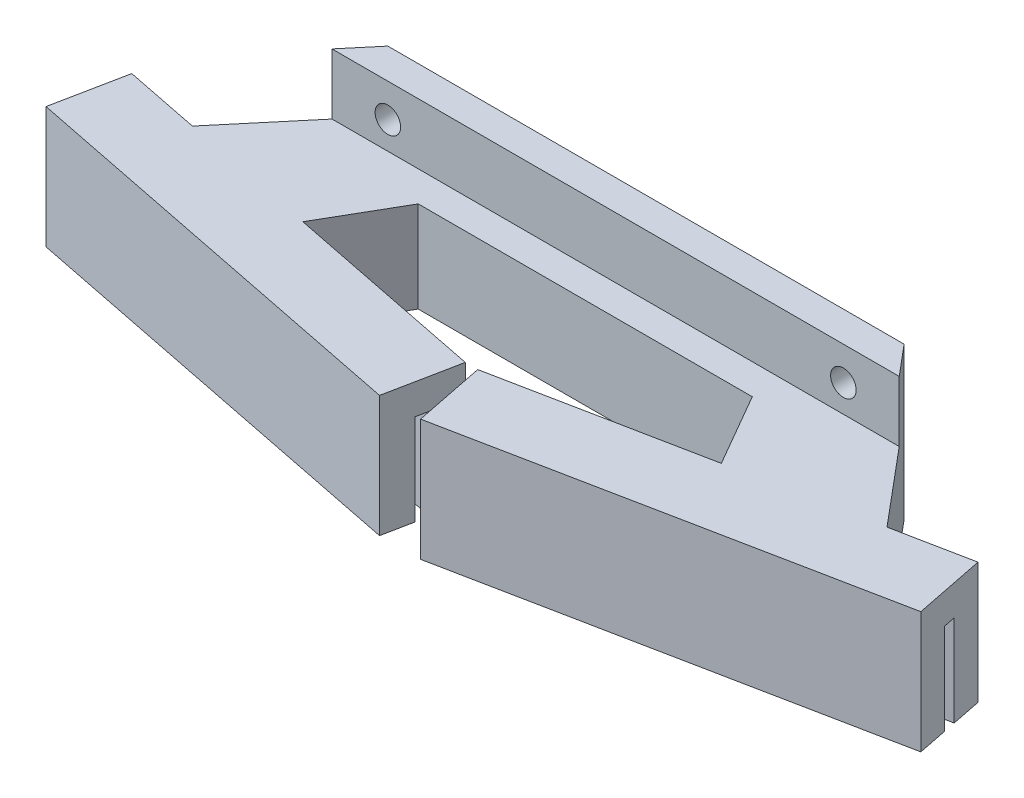
SolidWorks part; units mm, degrees
material "ABS"
ref_plane "Front Plane" through (0, 0, 0) normal (0, 0, 1) x (1, 0, 0)
ref_plane "Top Plane" through (0, 0, 0) normal (0, 1, 0) x (1, 0, 0)
ref_plane "Right Plane" through (0, 0, 0) normal (1, 0, 0) x (0, 0, -1)
ref_axis "X" through (-88.99, 0, 0) along (1, 0, 0)
ref_axis "Y" through (0, 55, 0) along (0, -1, 0)
ref_axis "Z" through (0, 0, -88.99) along (0, 0, 1)
sketch "Sketch1" plane through (0, 0, 0) normal (0, 1, 0) x (1, 0, 0)
  line L0 (27.1702, -94.8196) -> (27.5625, -96.7807) construction
  line L1 (27.1702, -94.8196) -> (27.5625, -96.7807)
  line L2 (22.7661, -96.7807) -> (23.1583, -94.8196) construction
  line L3 (-45.8746, -83.0526) -> (22.7661, -96.7807) construction
  line L4 (22.7661, -96.7807) -> (23.1583, -94.8196)
  line L5 (27.5625, -96.7807) -> (96.2031, -83.0526) construction
  line L6 (23.1583, -94.8196) -> (-45.4823, -81.0914)
  line L7 (-45.4823, -81.0914) -> (-45.8746, -83.0526)
  line L8 (-45.8746, -83.0526) -> (22.7661, -96.7807)
  line L9 (27.1702, -94.8196) -> (95.8109, -81.0914)
  line L10 (95.8109, -81.0914) -> (96.2031, -83.0526)
  line L11 (96.2031, -83.0526) -> (27.5625, -96.7807)
  dimension "D3" = 2
  dimension "D4" = 2
  dimension "D7" = 70
  dimension "D8" = 70
extrude "Boss-Extrude1" add sketch "Sketch1" along normal blind 5
sketch "Sketch2" plane through (0, 5, 0) normal (0, 1, 0) x (1, 0, 0)
  line L0 (0, 0) -> (0, 33.2136) construction
  line L1 (22.9622, -95.8001) -> (-45.6785, -82.072) construction
  line L2 (22.7661, -96.7807) -> (23.1583, -94.8196) construction
  line L3 (-45.4823, -81.0914) -> (-45.8746, -83.0526) construction
  line L4 (-45.4823, -81.0914) -> (-44.5018, -76.1885)
  line L5 (-44.5018, -76.1885) -> (24.1389, -89.9167)
  line L6 (24.1389, -89.9167) -> (23.1583, -94.8196)
  line L7 (23.1583, -94.8196) -> (-45.4823, -81.0914) construction
  line L8 (23.1583, -94.8196) -> (-45.4823, -81.0914)
  line L9 (21.7855, -101.6836) -> (22.7661, -96.7807)
  line L10 (-46.8552, -87.9555) -> (21.7855, -101.6836)
  line L11 (-45.8746, -83.0526) -> (-46.8552, -87.9555)
  line L12 (22.7661, -96.7807) -> (-45.8746, -83.0526)
  line L21 (27.1702, -94.8196) -> (26.1896, -89.9167)
  line L22 (26.1896, -89.9167) -> (94.8303, -76.1885)
  line L23 (94.8303, -76.1885) -> (95.8109, -81.0914)
  line L24 (96.2031, -83.0526) -> (95.8109, -81.0914) construction
  line L25 (95.8109, -81.0914) -> (27.1702, -94.8196) construction
  line L26 (95.8109, -81.0914) -> (27.1702, -94.8196)
  line L27 (27.3663, -95.8001) -> (96.007, -82.072) construction
  line L28 (27.1702, -94.8196) -> (27.5625, -96.7807) construction
  line L29 (97.1837, -87.9555) -> (96.2031, -83.0526)
  line L30 (28.543, -101.6836) -> (97.1837, -87.9555)
  line L31 (27.5625, -96.7807) -> (28.543, -101.6836)
  line L32 (96.2031, -83.0526) -> (27.5625, -96.7807)
  dimension "D1" = 5
  dimension "D2" = 5
extrude "Boss-Extrude2" add sketch "Sketch2" against normal blind 20
ref_plane "Plane1" through (0, -10, 0) normal (0, 1, 0) x (1, 0, 0)
sketch "Sketch3" plane through (0, -10, 0) normal (0, 1, 0) x (1, 0, 0)
  line L0 (25.1643, -107.258) -> (25.1643, -89.9167) construction
  line L1 (-17.3357, -61.1885) -> (67.6643, -61.1885)
  line L3 (-2.3357, -71.1885) -> (52.6643, -71.1885)
  line L5 (24.1389, -89.9167) -> (26.1896, -89.9167) construction
  line L6 (-17.3357, -61.1885) -> (-32.0174, -78.6854)
  line L7 (24.1389, -89.9167) -> (-44.5018, -76.1885) construction
  line L8 (-2.3357, -71.1885) -> (-9.2886, -83.2312)
  line L9 (67.6643, -61.1885) -> (82.3459, -78.6854)
  line L10 (94.8303, -76.1885) -> (26.1896, -89.9167) construction
  line L11 (52.6643, -71.1885) -> (59.6171, -83.2312)
  line L12 (-32.0174, -78.6854) -> (-9.2886, -83.2312)
  line L13 (59.6171, -83.2312) -> (82.3459, -78.6854)
  point P5 (25.1643, -71.1885)
  point P10 (25.1643, -89.9167)
  dimension "D1" = 10
  dimension "D2" = 15
  dimension "D3" = 15
  dimension "D4" = 85
  dimension "D5" = 120
  dimension "D6" = 120
  dimension "D7" = 130
  dimension "D8" = 130
  dimension "D9" = 15
extrude "Boss-Extrude3" add sketch "Sketch3" along normal blind 5
sketch "Sketch4" plane through (0, -5, 0) normal (0, 1, 0) x (1, 0, 0)
  line L0 (-17.3357, -61.1885) -> (-17.3357, -56.1885)
  line L1 (-17.3357, -56.1885) -> (67.6643, -56.1885)
  line L2 (67.6643, -56.1885) -> (67.6643, -61.1885)
  line L3 (67.6643, -61.1885) -> (-17.3357, -61.1885)
  dimension "D1" = 5
extrude "Boss-Extrude4" add sketch "Sketch4" against normal up to surface (5 mm away) up to face at (25.1643, -10, 73.5734)
sketch "Sketch5" plane through (0, -5, 0) normal (0, 1, 0) x (1, 0, 0)
  line L0 (25.1643, -71.1885) -> (25.1643, -56.1885) construction
  line L7 (-21.5312, -66.1885) -> (71.8598, -66.1885)
  line L9 (-2.3357, -71.1885) -> (52.6643, -71.1885) construction
  line L10 (67.6643, -56.1885) -> (-17.3357, -56.1885) construction
  line L13 (82.3459, -78.6854) -> (67.6643, -61.1885) construction
  line L14 (-17.3357, -61.1885) -> (67.6643, -61.1885)
  line L16 (-17.3357, -56.1885) -> (-17.3357, -61.1885) construction
  line L17 (67.6643, -61.1885) -> (67.6643, -56.1885) construction
  line L18 (67.6643, -61.1885) -> (71.8598, -66.1885)
  line L19 (-21.5312, -66.1885) -> (-17.3357, -61.1885)
  point P10 (25.1643, -66.1885)
  dimension "D1" = 5
  dimension "D3" = 5
extrude "Boss-Extrude5" add sketch "Sketch5" along normal blind 20
sketch "Sketch7" plane through (0, 0, 66.1885) normal (0, 0, 1) x (1, 0, 0)
  line L0 (-12.3357, 9.5) -> (62.6643, 9.5) construction
  line L1 (25.1643, 15) -> (25.1643, -5) construction
  line L2 (-21.5312, 15) -> (71.8598, 15) construction
  line L3 (-2.3357, -5) -> (52.6643, -5) construction
  line L4 (-21.5312, -5) -> (71.8598, -5) construction
  circle A0 centre (-12.3357, 9.5) radius 2.1
  circle A1 centre (62.6643, 9.5) radius 2.1
  point P10 (25.1643, 9.5)
  dimension "D1" = 4.2
  dimension "D2" = 75
  dimension "D3" = 14.5
extrude "Cut-Extrude1" cut sketch "Sketch7" against normal up to surface (5 mm away) up to face at (25.1643, 5, 61.1885)
sketch "Sketch8" plane through (0, -5, 0) normal (0, 1, 0) x (1, 0, 0)
  line L0 (59.6171, -83.2312) -> (82.3459, -78.6854) construction
  line L1 (52.6643, -71.1885) -> (59.6171, -83.2312) construction
  line L2 (82.3459, -78.6854) -> (71.8598, -66.1885) construction
  line L3 (-2.3357, -71.1885) -> (52.6643, -71.1885) construction
  line L4 (-9.2886, -83.2312) -> (-2.3357, -71.1885) construction
  line L5 (-21.5312, -66.1885) -> (71.8598, -66.1885) construction
  line L6 (-32.0174, -78.6854) -> (-9.2886, -83.2312) construction
  line L7 (-21.5312, -66.1885) -> (-32.0174, -78.6854) construction
  line L8 (59.6171, -83.2312) -> (82.3459, -78.6854)
  line L9 (52.6643, -71.1885) -> (59.6171, -83.2312)
  line L10 (82.3459, -78.6854) -> (71.8598, -66.1885)
  line L11 (-2.3357, -71.1885) -> (52.6643, -71.1885)
  line L12 (-9.2886, -83.2312) -> (-2.3357, -71.1885)
  line L13 (-21.5312, -66.1885) -> (71.8598, -66.1885)
  line L14 (-32.0174, -78.6854) -> (-9.2886, -83.2312)
  line L15 (-21.5312, -66.1885) -> (-32.0174, -78.6854)
extrude "Boss-Extrude6" add sketch "Sketch8" along normal up to surface (10 mm away) up to face at (-11.3581, 5, 88.9361)
sketch "Sketch11" plane through (0, -5, 0) normal (0, 1, 0) x (1, 0, 0)
  line L1 (-17.3357, -56.1885) -> (67.6643, -56.1885)
  line L2 (-17.3357, -56.1885) -> (-17.3357, -61.1885)
  line L3 (-17.3357, -61.1885) -> (67.6643, -61.1885)
  line L4 (67.6643, -56.1885) -> (67.6643, -61.1885)
extrude "Cut-Extrude2" cut sketch "Sketch11" against normal up to surface (5 mm away) up to face at (25.1643, -10, 70.0964)
